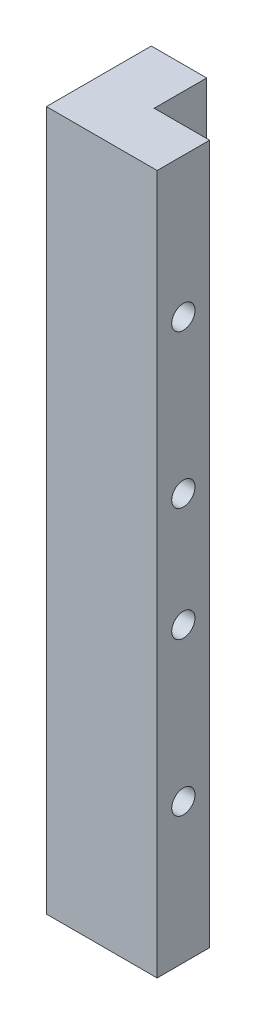
SolidWorks part; units mm, degrees
ref_plane "Front Plane" through (0, 0, 0) normal (0, 0, 1) x (1, 0, 0)
ref_plane "Top Plane" through (0, 0, 0) normal (0, 1, 0) x (1, 0, 0)
ref_plane "Right Plane" through (0, 0, 0) normal (1, 0, 0) x (0, 0, -1)
sketch "Sketch1" plane through (0, 0, 0) normal (0, 1, 0) x (1, 0, 0)
  line L0 (0, -55) -> (0, 55) construction
  line L1 (-9.5, -4.5) -> (9.5, -4.5)
  line L2 (-9.5, -4.5) -> (-9.5, 4.5)
  line L3 (-9.5, 4.5) -> (9.5, 4.5)
  line L4 (9.5, -4.5) -> (9.5, 4.5)
  line L5 (-9.5, -4.5) -> (9.5, 4.5) construction
  line L6 (-9.5, 4.5) -> (9.5, -4.5) construction
  line L7 (-9.5, 4.5) -> (0, 4.5)
  line L8 (-9.5, 4.5) -> (-9.5, 13.5)
  line L9 (-9.5, 13.5) -> (0, 13.5)
  line L10 (0, 4.5) -> (0, 13.5)
  point P0 (0, 0)
  dimension "D1" = 9
  dimension "D2" = 19
  dimension "D3" = 9
  dimension "D4" = 9.5
extrude "Boss-Extrude1" add sketch "Sketch1" along normal blind 120 contours L1 L4 L3 L2 | L3 | L3 L10 L9 L8 region at (0, 0, 0) region at (-4.75, 0, -9)
sketch "Sketch2" plane through (9.5, 0, -9.5) normal (-1, 0, 0) x (0, 0, 1)
  line L0 (9.5, 0) -> (9.5, 120)
  line L2 (34.1, 19.5) -> (9.5, 19.5)
  line L3 (34.1, 54.75) -> (9.5, 54.75)
  line L4 (34.1, 65.25) -> (9.5, 65.25)
  line L5 (34.1, 100.5) -> (9.5, 100.5)
  line L6 (34.1, 60) -> (9.5, 60)
  line L16 (34.1, 120) -> (-22.7, 120)
  line L17 (-22.7, 120) -> (-22.7, 0)
  line L18 (-22.7, 0) -> (34.1, 0)
  line L19 (34.1, 0) -> (34.1, 120)
  circle A0 centre (9.5, 24) radius 2
  circle A1 centre (9.5, 50.25) radius 2
  circle A2 centre (9.5, 69.75) radius 2
  circle A3 centre (9.5, 96) radius 2
  dimension "D1" = 4
  dimension "D3" = 4
  dimension "D2" = 4.5
  dimension "D4" = 4.5
extrude "Cut-Extrude1" cut sketch "Sketch2" along normal blind 19 contours A3 | A2 | A1 | A0
